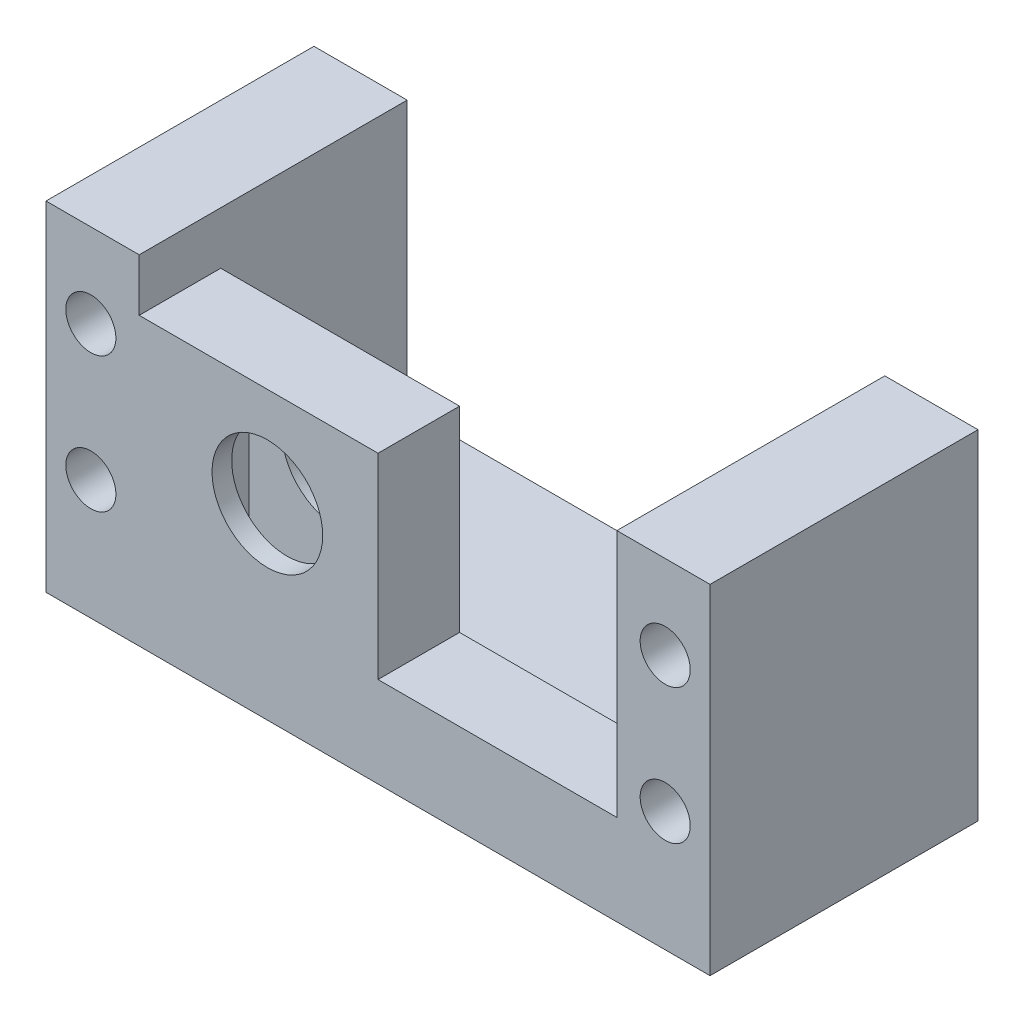
SolidWorks part; units mm, degrees
ref_plane "Спереди" through (0, 0, 0) normal (0, 0, 1) x (1, 0, 0)
ref_plane "Сверху" through (0, 0, 0) normal (0, 1, 0) x (1, 0, 0)
ref_plane "Справа" through (0, 0, 0) normal (1, 0, 0) x (0, 0, -1)
sketch "Эскиз1" plane through (0, 0, 0) normal (0, 0, 1) x (1, 0, 0)
  line L2 (-59.1906, -40.1769) -> (-59.1906, -15.0857)
  line L3 (-59.1906, -15.0857) -> (-51.1906, -15.0857)
  line L4 (-2.1906, -38.0857) -> (-2.1906, -15.0857)
  line L8 (-2.1906, -15.0857) -> (-10.1906, -15.0857)
  line L9 (-10.1906, -15.0857) -> (-10.1906, -38.0857)
  line L10 (-51.1906, -15.0857) -> (-51.1906, -38.0857)
  line L11 (-51.1906, -38.0857) -> (-10.1906, -38.0857)
  line L12 (-59.1906, -40.1769) -> (-59.1906, -44.1769)
  line L13 (-59.1906, -44.1769) -> (-2.1906, -44.1769)
  line L14 (-2.1906, -44.1769) -> (-2.1906, -38.0857)
  point P0 (0, 0)
extrude "Бобышка-Вытянуть1" add sketch "Эскиз1" along normal blind 23
sketch "Эскиз3" plane through (-59.1906, 0, 0) normal (-1, 0, 0) x (0, 0, 1)
  line L5 (0, -15.0857) -> (0, -44.1769) construction
  line L6 (15, -15.0857) -> (0, -15.0857) construction
  line L7 (15, -15.0857) -> (15, -38.2478) construction
  line L8 (15, -38.2478) -> (0, -38.2478) construction
  line L9 (0, -15.0857) -> (0, -38.2478) construction
sketch "Эскиз5" plane through (0, 0, 23) normal (0, 0, 1) x (1, 0, 0)
  line L0 (-51.1906, -38.0857) -> (-51.1906, -15.0857) construction
  line L1 (-10.1906, -28.0857) -> (-24.1906, -28.0857) construction
  line L6 (-30.6906, -18.0857) -> (-30.6906, -34.9839) construction
  line L11 (-51.1906, -28.0857) -> (-37.1906, -28.0857) construction
  line L12 (-10.1906, -38.0857) -> (-51.1906, -38.0857) construction
  line L13 (-10.1906, -38.0857) -> (-10.1906, -18.0857) construction
  line L14 (-10.1906, -18.0857) -> (-51.1906, -18.0857) construction
  line L15 (-51.1906, -38.0857) -> (-51.1906, -18.0857) construction
  line L16 (-21.1906, -34.9839) -> (-51.1906, -34.9839) construction
  line L18 (-21.1906, -19.5857) -> (-51.1906, -19.5857)
  line L19 (-51.1906, -34.9839) -> (-51.1906, -19.5857)
  line L20 (-21.1906, -19.5857) -> (-10.1906, -19.5857)
  line L22 (-21.1906, -34.9839) -> (-10.1906, -34.9839) construction
  line L23 (-10.1906, -19.5857) -> (-10.1906, -34.9839)
  line L24 (-10.1906, -38.0857) -> (-51.1906, -38.0857)
  line L25 (-51.1906, -38.0857) -> (-51.1906, -34.9839)
  line L26 (-10.1906, -38.0857) -> (-10.1906, -34.9839)
  circle A5 centre (-21.1906, -28.0857) radius 2.7
  circle A6 centre (-40.1906, -28.0857) radius 4.75
extrude "Бобышка-Вытянуть6" add sketch "Эскиз5" against normal blind 7
sketch "Эскиз6" plane through (0, 0, 23) normal (0, 0, 1) x (1, 0, 0)
  line L0 (-51.1906, -19.5857) -> (-51.1906, -15.0857) construction
  line L3 (-10.1906, -18.0857) -> (-51.1906, -18.0857)
  line L4 (-51.1906, -38.0857) -> (-51.1906, -18.0857)
  line L5 (-2.1906, -38.0857) -> (-59.1906, -38.0857) construction
  line L6 (-2.1906, -44.1769) -> (-2.1906, -15.0857) construction
  line L7 (-6.0406, -38.0857) -> (-6.0406, -29.5857) construction
  line L8 (-59.1906, -15.0857) -> (-59.1906, -44.1769) construction
  line L9 (-10.1906, -18.0857) -> (-2.1906, -18.0857) construction
  line L10 (-6.0406, -18.0857) -> (-6.0406, -26.5857) construction
  line L11 (-6.0406, -22.2857) -> (-10.1906, -22.2857) construction
  line L12 (-30.6906, -38.0857) -> (-30.6906, -18.0857) construction
  line L13 (-10.1906, -18.0857) -> (-10.1906, -38.0857) construction
  line L14 (-6.0406, -33.8857) -> (-10.1906, -33.8857) construction
  circle A1 centre (-6.0406, -33.8857) radius 2.15
  circle A3 centre (-6.0406, -22.2857) radius 2.15
  circle A4 centre (-55.3406, -22.2857) radius 2.15
  circle A5 centre (-55.3406, -33.8857) radius 2.15
extrude "Вырез-Вытянуть2" cut sketch "Эскиз6" against normal through all contours A1 | A3 | A5 | A4 region at (-6.0406, -33.8857, 23) region at (-6.0406, -22.2857, 23) region at (-55.3406, -22.2857, 23) region at (-55.3406, -33.8857, 23)
sketch "Эскиз8" plane through (0, 0, 23) normal (0, 0, 1) x (1, 0, 0)
  line L1 (-10.1906, -19.5857) -> (-30.6906, -19.5857)
  line L2 (-10.1906, -19.5857) -> (-10.1906, -36.4088)
  line L3 (-10.1906, -36.4088) -> (-30.6906, -36.4088)
  line L4 (-30.6906, -19.5857) -> (-30.6906, -36.4088)
extrude "Вырез-Вытянуть4" cut sketch "Эскиз8" against normal up to surface (7 mm away) up to face at (-44.9406, -28.0857, 16)
sketch "Эскиз14" plane through (0, -44.1769, 0) normal (0, -1, 0) x (-1, 0, 0)
  line L0 (41.1237, -23) -> (41.1237, -19.1629) construction
  line L1 (59.1906, -23) -> (2.1906, -23) construction
  line L3 (34.4737, -21.3129) -> (47.7737, -21.3129)
  line L4 (34.4737, -21.3129) -> (34.4737, -17.0129)
  line L5 (34.4737, -17.0129) -> (47.7737, -17.0129)
  line L6 (47.7737, -21.3129) -> (47.7737, -17.0129)
  line L7 (34.4737, -21.3129) -> (47.7737, -17.0129) construction
  line L8 (34.4737, -17.0129) -> (47.7737, -21.3129) construction
extrude "Вырез-Вытянуть7" cut sketch "Эскиз14" against normal blind 22.74
sketch "Эскиз16" plane through (0, 0, 23) normal (0, 0, 1) x (1, 0, 0)
  line L0 (-40.1906, -21.4357) -> (-40.1906, -34.7357)
  line L1 (-40.1906, -21.4357) -> (-43.9534, -21.4357) construction
  line L2 (-43.9534, -21.4357) -> (-43.9534, -44.1769) construction
  line L3 (-59.1906, -44.1769) -> (-2.1906, -44.1769) construction
  point P4 (-40.1906, -28.0857)
